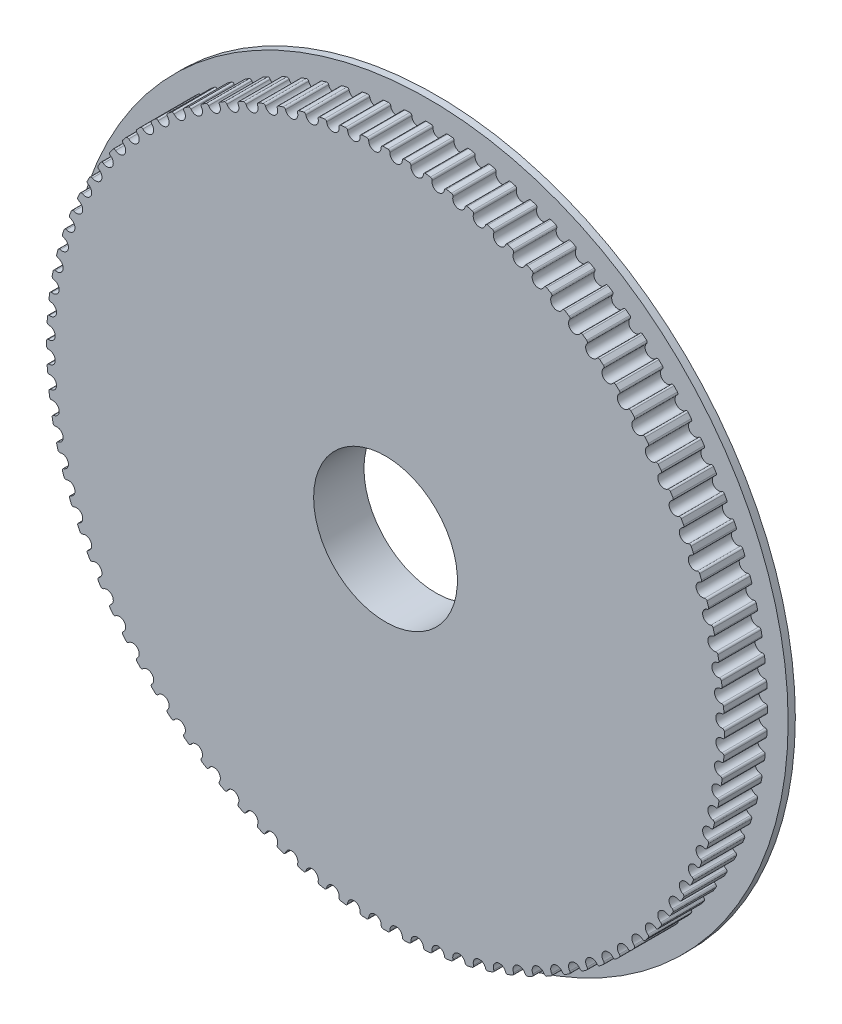
SolidWorks part; units mm, degrees
ref_plane "Front Plane" through (0, 0, 0) normal (1, 0, 0) x (0, 1, 0)
ref_plane "Top Plane" through (0, 0, 0) normal (0, 0, 1) x (0, 1, 0)
ref_plane "Right Plane" through (0, 0, 0) normal (0, 1, 0) x (-1, 0, 0)
sketch "Reference" plane through (0, 0, 0) normal (0, 0, 1) x (0, 1, 0)
  line L0 (-61.0617, -60.1433) -> (-46.7747, 9.5841)
  line L1 (-48.594, -70.6001) -> (17.5811, -44.3918)
  arc A0 (17.5811, -44.3918) -> (-46.7747, 9.5841) centre (0, 0) ccw
  arc A1 (-61.0617, -60.1433) -> (-48.594, -70.6001) centre (-52, -62) ccw
  dimension "D1" = 95.493
  dimension "D2" = 18.5
  dimension "D3" = 52
  dimension "D4" = 62
sketch "Sketch4" plane through (0, 0, 0) normal (0, 0, 1) x (0, 1, 0)
  line L0 (0, 0) -> (0, 47.1315)
  line L1 (0, 0) -> (1.4437, 45.9388) construction
  line L2 (0, 0) -> (2.9594, 47.0385)
  line L3 (1.4437, 45.9388) -> (1.471, 46.8084) construction
  arc A0 (0.6619, 47.1268) -> (2.2986, 47.0754) centre (1.471, 46.8084) ccw
  arc A1 (0, 47.1315) -> (0.6619, 47.1268) centre (0, 0) cw
  arc A2 (2.2986, 47.0754) -> (2.9594, 47.0385) centre (0, 0) cw
  dimension "D1" = 47.1315
  dimension "D2" = 45.9615
  dimension "D3" = 47.1315
  dimension "D4" = 1.8
  dimension "D5" = 1.8
  dimension "D6" = 0.87
extrude "Boss-Extrude1" add sketch "Sketch4" along normal blind 6 contours A2 A0 A1 L0 L2 region at (-31.0221, 0.9749, 0)
fillet "Fillet1" radius 0.26 2 edges at (-47.0754, 2.2986, 3) (-47.1268, 0.6619, 3)
pattern_circular "CirPattern1" count 100 over 360 about axis through (0, 0, 6) along (0, 0, -1) of "Fillet1", "Boss-Extrude1"
sketch "Sketch5" plane through (0, 0, 0) normal (0, 0, -1) x (1, 0, 0)
  circle A0 centre (0, 0) radius 50
  circle A1 centre (0, 0) radius 10
  dimension "D1" = 100
  dimension "D2" = 20
extrude "Boss-Extrude2" add sketch "Sketch5" along normal blind 1 contours A1 | A0 A1 region at (-48.5858, 0, 0) region at (0, 0, 0)
extrude "Cut-Extrude1" cut sketch "Sketch5<3>" against normal through all both and the other way through all contours A1
sketch "Sketch5<3>" plane through (0, 0, 0) normal (0, 0, -1) x (1, 0, 0) same geometry as "Sketch5"
equation "\"Pitch\"= 3mm"
equation "\"Teeth\" = 100"
equation "\"BeltHeight\" = 5 + 1 * 1mm"
equation "\"PitchDiameter\"= \"Pitch\" * \"Teeth\" / PI * 1mm"
equation "\"D1@Reference\" = \"PitchDiameter\""
equation "\"D1@Sketch4\"=\"PitchDiameter\"/2 - 0.615"
equation "\"D2@Sketch4\"=\"D1@Sketch4\"-1.17"
equation "\"D3@Sketch4\"=\"D1@Sketch4\""
equation "\"D4@Sketch4\"=180 / \"Teeth\""
equation "\"D5@Sketch4\"=\"D4@Sketch4\""
equation "\"D1@Boss-Extrude1\"=\"BeltHeight\""
equation "\"D1@CirPattern1\"=\"Teeth\""
